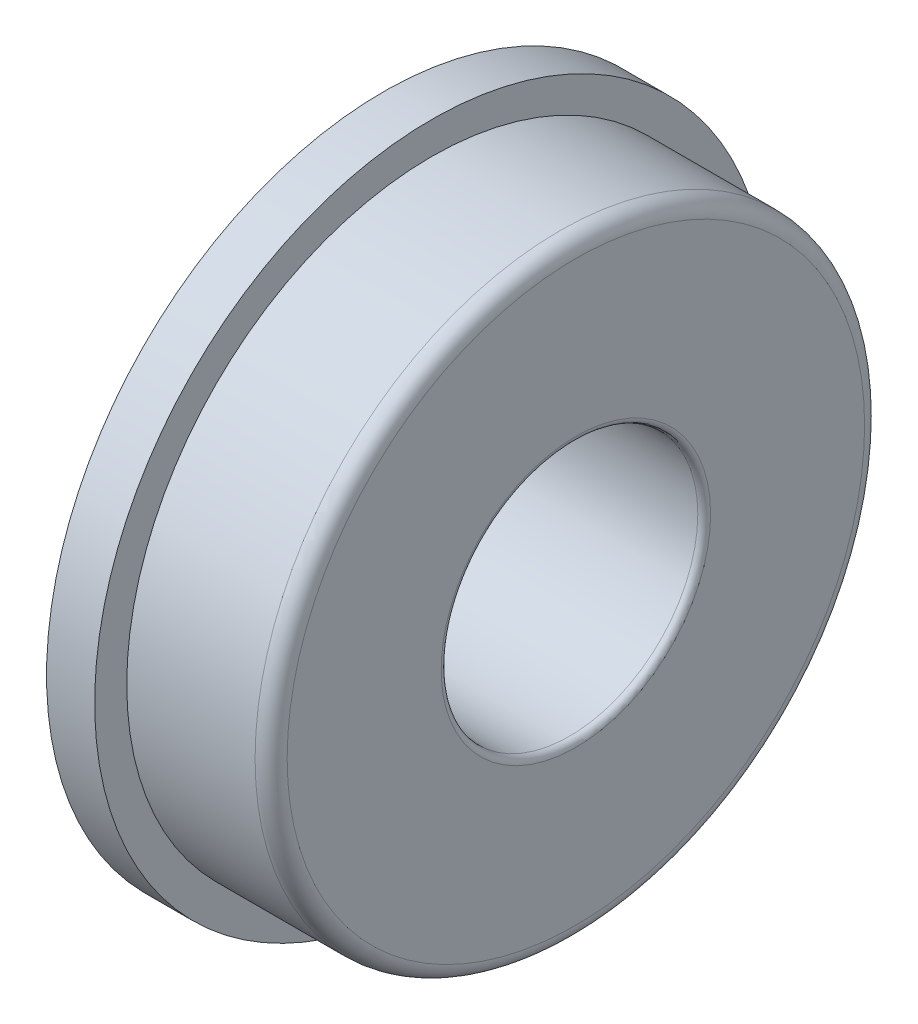
SolidWorks part; units mm, degrees
ref_plane "Front Plane" through (0, 0, 0) normal (1, 0, 0) x (0, 1, 0)
ref_plane "Top Plane" through (0, 0, 0) normal (0, 0, 1) x (0, 1, 0)
ref_plane "Right Plane" through (0, 0, 0) normal (0, 1, 0) x (-1, 0, 0)
sketch "Sketch2" plane through (0, 0, 0) normal (1, 0, 0) x (0, 1, 0)
  circle A0 centre (0, 0) radius 10.5
  dimension "D1" = 21
extrude "Boss-Extrude1" add sketch "Sketch2" along normal blind 1.5
sketch "Sketch3" plane through (1.5, 0, 0) normal (1, 0, 0) x (0, 1, 0)
  circle A0 centre (0, 0) radius 9.5
  dimension "D1" = 19
extrude "Boss-Extrude2" add sketch "Sketch3" along normal blind 4.5
sketch "Sketch4" plane through (6, 0, 0) normal (1, 0, 0) x (0, 1, 0)
  circle A0 centre (0, 0) radius 4
  dimension "D1" = 8
extrude "Cut-Extrude1" cut sketch "Sketch4" against normal up to surface (6 mm away) up to face at (0, 0, -10.5)
fillet "Fillet1" radius 0.5 1 edges at (6, 0, -9.5)
fillet "Fillet2" radius 0.2 2 edges at (6, 0, -4) (0, 0, -4)
sketch "Sketch5" plane through (0, 0, 0) normal (-1, 0, 0) x (0, -1, 0)
  circle A0 centre (0, 0) radius 8.5
  circle A1 centre (0, 0) radius 6
  dimension "D1" = 17
  dimension "D2" = 12
extrude "Cut-Extrude2" cut sketch "Sketch5" against normal blind 0.5 contours A0 | A1
